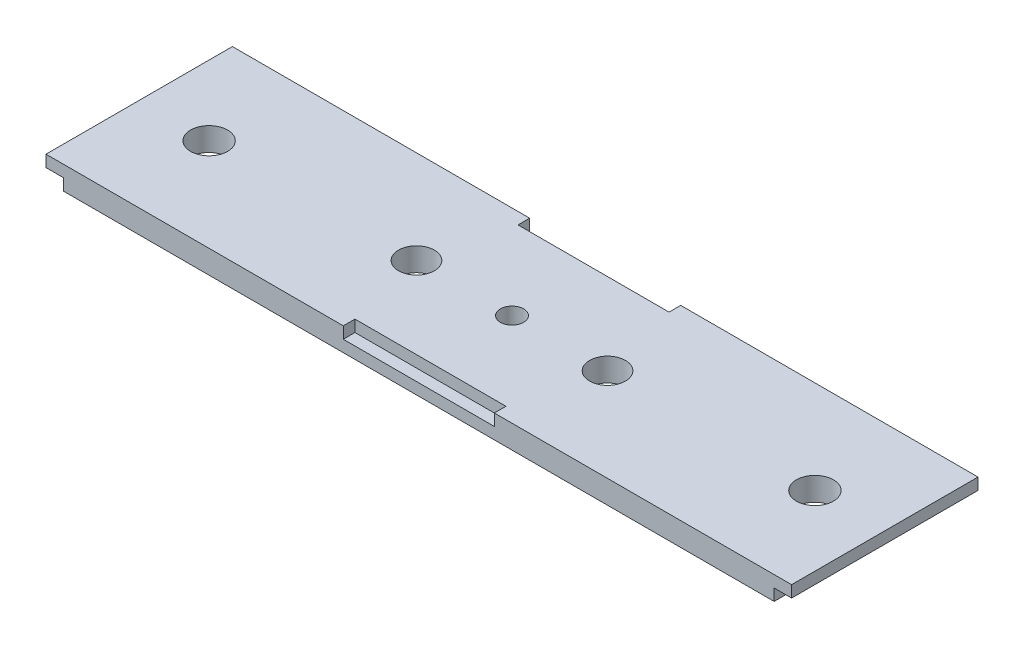
SolidWorks part; units mm, degrees
ref_plane "Front Plane" through (0, 0, 0) normal (0, 0, 1) x (1, 0, 0)
ref_plane "Top Plane" through (0, 0, 0) normal (0, 1, 0) x (1, 0, 0)
ref_plane "Right Plane" through (0, 0, 0) normal (1, 0, 0) x (0, 0, -1)
sketch "Sketch1" plane through (0, 0, 0) normal (0, 1, 0) x (1, 0, 0)
  line L0 (-101.6, 0) -> (-82.55, 0) construction
  line L1 (-101.6, -25.4) -> (101.6, -25.4)
  line L2 (-101.6, -25.4) -> (-101.6, 25.4)
  line L3 (-101.6, 25.4) -> (101.6, 25.4)
  line L4 (101.6, -25.4) -> (101.6, 25.4)
  line L5 (-101.6, -25.4) -> (101.6, 25.4) construction
  line L6 (-101.6, 25.4) -> (101.6, -25.4) construction
  line L7 (-15.5, 15.5) -> (15.5, 15.5) construction
  line L8 (-15.5, 15.5) -> (-15.5, -15.5) construction
  line L11 (-15.5, 15.5) -> (15.5, -15.5) construction
  line L12 (-15.5, -15.5) -> (15.5, 15.5) construction
  line L13 (0, 25.4) -> (0, -25.4) construction
  line L14 (101.6, 0) -> (82.55, 0) construction
  line L15 (-15.5, -15.5) -> (15.5, -15.5) construction
  line L16 (15.5, -15.5) -> (15.5, 15.5) construction
  circle A4 centre (-82.55, 0) radius 5.05
  circle A5 centre (82.55, 0) radius 5.05
  circle A6 centre (0, 0) radius 3.175
  point P0 (0, 0)
  point P6 (0, 0)
  point P21 (0, 0)
  dimension "D7" = 10.1
  dimension "D8" = 6.35
  dimension "D1" = 203.2
  dimension "D2" = 50.8
  dimension "D3" = 31
  dimension "D6" = 19.05
  dimension "D9" = 82.55
extrude "Boss-Extrude1" add sketch "Sketch1" along normal blind 6.35
sketch "Sketch2" plane through (0, 6.35, 0) normal (0, 1, 0) x (1, 0, 0)
  line L0 (-15.5, -15.5) -> (-20.58, -15.5) construction
  line L3 (15.5, -15.5) -> (20.58, -15.5) construction
  line L4 (20.58, -25.4) -> (20.58, -22.225)
  line L5 (-101.6, -25.4) -> (101.6, -25.4) construction
  line L6 (20.58, -22.225) -> (-20.58, -22.225)
  line L7 (-20.58, -22.225) -> (-20.58, -25.4)
  line L8 (-20.58, -25.4) -> (20.58, -25.4)
  line L9 (-82.55, 0) -> (82.55, 0) construction
  line L10 (-20.58, 25.4) -> (20.58, 25.4)
  line L11 (-20.58, 22.225) -> (-20.58, 25.4)
  line L12 (20.58, 22.225) -> (-20.58, 22.225)
  line L13 (20.58, 25.4) -> (20.58, 22.225)
  dimension "D1" = 5.08
  dimension "D2" = 3.175
extrude "Cut-Extrude1" cut sketch "Sketch2" against normal blind 3.175
sketch "Sketch3" plane through (0, 0, 0) normal (0, -1, 0) x (1, 0, 0)
  line L0 (-101.6, 25.4) -> (-96.8375, 25.4)
  line L3 (-101.6, 25.4) -> (101.6, 25.4) construction
  line L6 (101.6, -25.4) -> (-101.6, -25.4) construction
  line L8 (0, 25.4) -> (0, -25.4) construction
  line L13 (-96.8375, 25.4) -> (-96.8375, -25.4)
  line L14 (-96.8375, -25.4) -> (-101.6, -25.4)
  line L16 (-101.6, -25.4) -> (-101.6, 25.4) construction
  line L17 (-101.6, -25.4) -> (-101.6, 25.4)
  line L18 (101.6, -25.4) -> (101.6, 25.4)
  line L19 (96.8375, -25.4) -> (101.6, -25.4)
  line L20 (96.8375, 25.4) -> (96.8375, -25.4)
  line L21 (101.6, 25.4) -> (96.8375, 25.4)
  dimension "D1" = 4.7625
extrude "Cut-Extrude2" cut sketch "Sketch3" against normal blind 3.175
sketch "Sketch4" plane through (0, 6.35, 0) normal (0, 1, 0) x (1, 0, 0)
  line L0 (0, 25.4) -> (0, -25.4) construction
  line L1 (20.58, 25.4) -> (-20.58, 25.4) construction
  line L2 (-20.58, -25.4) -> (20.58, -25.4) construction
  circle A0 centre (0, 0) radius 7.62 construction
  circle A1 centre (-26.035, 0) radius 18.415 construction
  circle A3 centre (-26.035, 0) radius 4.8895
  circle A4 centre (26.035, 0) radius 4.8895
  circle A6 centre (-82.55, 0) radius 38.1 construction
  dimension "D1" = 15.24
  dimension "D2" = 36.83
  dimension "D3" = 76.2
  dimension "D4" = 9.779
extrude "Cut-Extrude3" cut sketch "Sketch4" against normal through all
